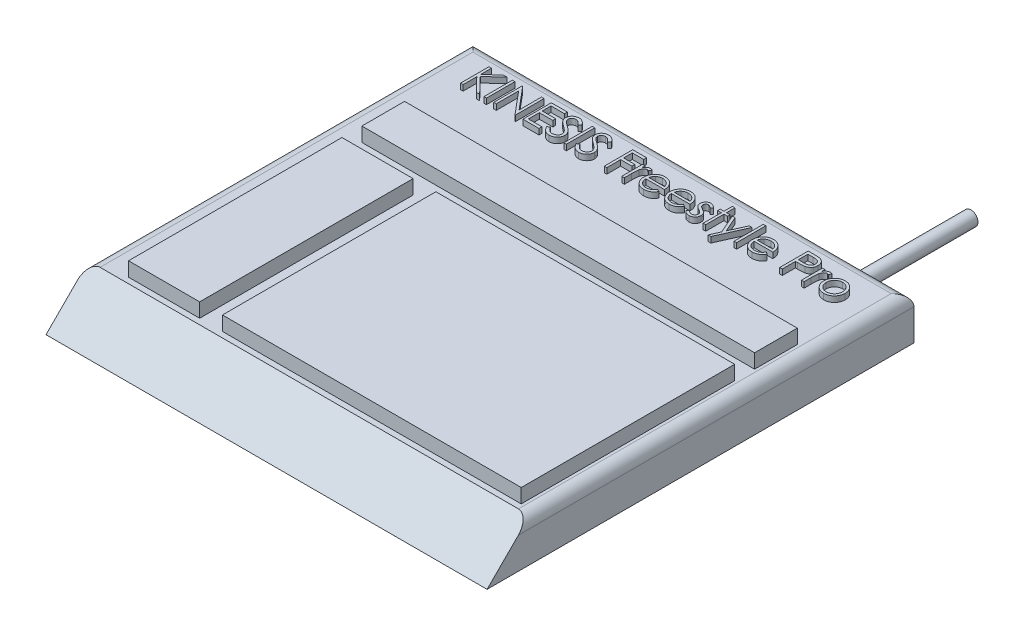
SolidWorks part; units mm, degrees
ref_plane "Front Plane" through (0, 0, 0) normal (0, 0, 1) x (1, 0, 0)
ref_plane "Top Plane" through (0, 0, 0) normal (0, 1, 0) x (1, 0, 0)
ref_plane "Right Plane" through (0, 0, 0) normal (1, 0, 0) x (0, 0, -1)
sketch "Sketch1" plane through (0, 0, 0) normal (0, 1, 0) x (1, 0, 0)
  line L1 (0, 0) -> (196.85, 0)
  line L2 (0, 0) -> (0, -165.1)
  line L3 (0, -165.1) -> (196.85, -165.1)
  line L4 (196.85, 0) -> (196.85, -165.1)
  dimension "D1" = 165.1
  dimension "D3" = 196.85
extrude "Boss-Extrude1" add sketch "Sketch1" along normal blind 19.05
sketch "Sketch2" plane through (0, 0, 0) normal (0, 1, 0) x (1, 0, 0)
  line L0 (0, -165.1) -> (196.85, -165.1)
  line L1 (0, -165.1) -> (0, -190.5)
  line L2 (196.85, -165.1) -> (196.85, -190.5)
  line L3 (0, -190.5) -> (196.85, -190.5)
  dimension "D1" = 25.4
extrude "Boss-Extrude2" add sketch "Sketch2" along normal blind 19.05 contours L0 L1 L3 L2
chamfer "Chamfer1" distance 19.05 angle 45 1 edges at (98.425, 19.05, 190.5)
sketch "Sketch3" plane through (0, 19.05, 0) normal (0, 1, 0) x (1, 0, 0)
  line L0 (196.85, -171.45) -> (196.85, 0) construction
  line L1 (15.24, -168.91) -> (46.99, -168.91)
  line L2 (15.24, -168.91) -> (15.24, -73.66)
  line L3 (15.24, -73.66) -> (46.99, -73.66)
  line L4 (46.99, -168.91) -> (46.99, -73.66)
  line L5 (57.15, -168.91) -> (190.5, -168.91)
  line L6 (57.15, -168.91) -> (57.15, -73.66)
  line L7 (57.15, -73.66) -> (190.5, -73.66)
  line L8 (190.5, -168.91) -> (190.5, -73.66)
  line L9 (0, -171.45) -> (196.85, -171.45) construction
  line L10 (0, 0) -> (0, -171.45) construction
  line L11 (15.24, -45.72) -> (190.5, -45.72)
  line L12 (15.24, -45.72) -> (15.24, -64.77)
  line L13 (15.24, -64.77) -> (190.5, -64.77)
  line L14 (190.5, -45.72) -> (190.5, -64.77)
  dimension "D1" = 6.35
  dimension "D2" = 133.35
  dimension "D3" = 2.54
  dimension "D4" = 95.25
  dimension "D5" = 2.54
  dimension "D6" = 31.75
  dimension "D7" = 10.16
  dimension "D8" = 95.25
  dimension "D9" = 6.35
  dimension "D10" = 15.24
  dimension "D11" = 8.89
  dimension "D12" = 19.05
extrude "Boss-Extrude3" add sketch "Sketch3" along normal blind 6.35
sketch "Sketch4" plane through (0, 19.05, 0) normal (0, 1, 0) x (1, 0, 0)
  line L0 (15.24, -45.72) -> (15.24, -64.77) construction
  text T0 "KINESIS Freestyle Pro" font "Century Gothic" height 12.7
  dimension "D1" = 0
extrude "Boss-Extrude4" add sketch "Sketch4" along normal blind 2.54
sketch "Sketch5" plane through (0, 0, 0) normal (0, 0, -1) x (-1, 0, 0)
  line L0 (-196.85, 19.05) -> (0, 19.05) construction
  line L1 (-196.85, 19.05) -> (-196.85, 0) construction
  circle A0 centre (-171.45, 10.16) radius 3.175
  dimension "D3" = 6.35
  dimension "D1" = 8.89
  dimension "D2" = 25.4
extrude "Boss-Extrude5" add sketch "Sketch5" along normal blind 50.8
fillet "Fillet1" radius 5.08 3 edges at (98.425, 19.05, 0) (0, 19.05, 85.725) (196.85, 19.05, 85.725)
sketch "Sketch6" plane through (0, 0, 0) normal (0, -1, 0) x (1, 0, 0)
  line L0 (25.4, 179.07) -> (12.7, 179.07) construction
  line L1 (25.4, 172.72) -> (12.7, 172.72)
  line L2 (25.4, 185.42) -> (12.7, 185.42)
  line L3 (0, 190.5) -> (196.85, 190.5) construction
  line L4 (0, 0) -> (0, 190.5) construction
  line L5 (98.425, 190.5) -> (98.425, 55.114) construction
  line L6 (0, 95.25) -> (246.7978, 95.25) construction
  line L7 (171.45, 179.07) -> (184.15, 179.07) construction
  line L8 (171.45, 172.72) -> (184.15, 172.72)
  line L9 (171.45, 185.42) -> (184.15, 185.42)
  line L10 (171.45, 11.43) -> (184.15, 11.43) construction
  line L11 (171.45, 17.78) -> (184.15, 17.78)
  line L12 (171.45, 5.08) -> (184.15, 5.08)
  line L13 (25.4, 11.43) -> (12.7, 11.43) construction
  line L14 (25.4, 17.78) -> (12.7, 17.78)
  line L15 (25.4, 5.08) -> (12.7, 5.08)
  arc A0 (25.4, 172.72) -> (25.4, 185.42) centre (25.4, 179.07) ccw
  arc A1 (12.7, 185.42) -> (12.7, 172.72) centre (12.7, 179.07) ccw
  arc A2 (171.45, 172.72) -> (171.45, 185.42) centre (171.45, 179.07) cw
  arc A3 (184.15, 185.42) -> (184.15, 172.72) centre (184.15, 179.07) cw
  arc A4 (171.45, 17.78) -> (171.45, 5.08) centre (171.45, 11.43) ccw
  arc A5 (184.15, 5.08) -> (184.15, 17.78) centre (184.15, 11.43) ccw
  arc A6 (25.4, 17.78) -> (25.4, 5.08) centre (25.4, 11.43) cw
  arc A7 (12.7, 5.08) -> (12.7, 17.78) centre (12.7, 11.43) cw
  point P2 (19.05, 179.07)
  point P17 (177.8, 179.07)
  point P24 (177.8, 11.43)
  point P31 (19.05, 11.43)
  dimension "D1" = 6.35
  dimension "D2" = 12.7
  dimension "D3" = 5.08
  dimension "D4" = 19.05
extrude "Boss-Extrude6" add sketch "Sketch6" along normal blind 2.54
